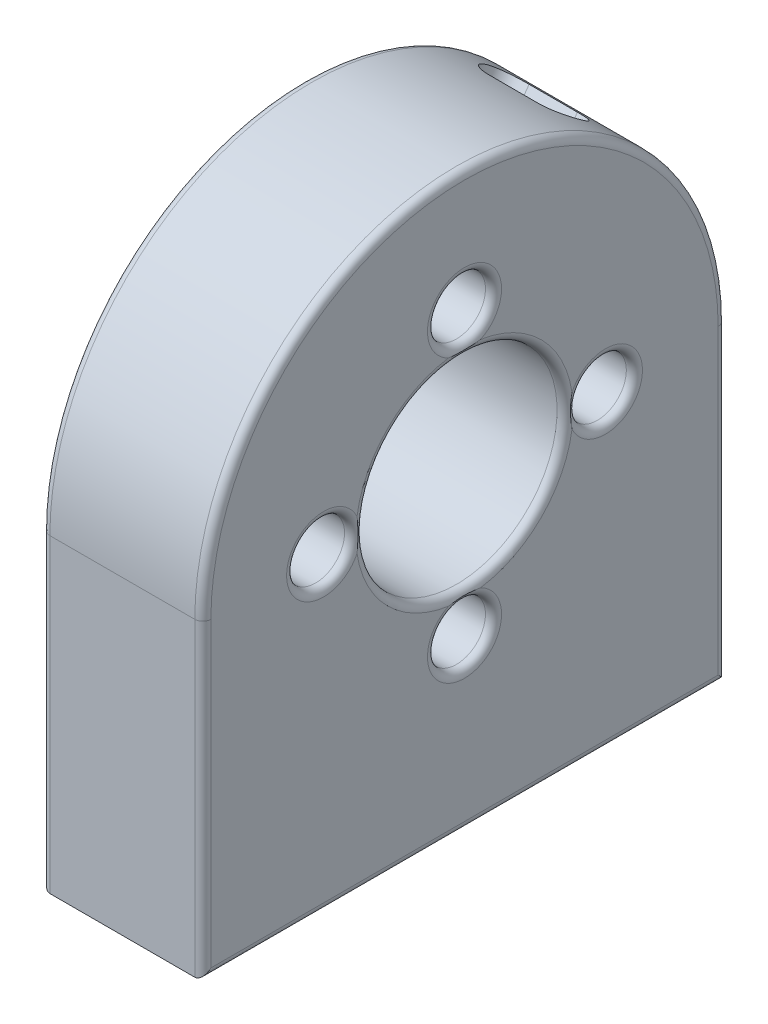
SolidWorks part; units mm, degrees
ref_plane "Ebene vorne" through (0, 0, 0) normal (0, 0, 1) x (1, 0, 0)
ref_plane "Ebene oben" through (0, 0, 0) normal (0, 1, 0) x (1, 0, 0)
ref_plane "Ebene rechts" through (0, 0, 0) normal (1, 0, 0) x (0, 0, -1)
sketch "Skizze1" plane through (0, 0, 0) normal (0, 1, 0) x (1, 0, 0)
  line L1 (-10, -32.5) -> (10, -32.5)
  line L2 (-10, -32.5) -> (-10, 32.5)
  line L3 (-10, 32.5) -> (10, 32.5)
  line L4 (10, -32.5) -> (10, 32.5)
  line L5 (-10, -32.5) -> (10, 32.5) construction
  line L6 (-10, 32.5) -> (10, -32.5) construction
  point P0 (0, 0)
  dimension "D1" = 20
  dimension "D2" = 65
extrude "Aufsatz-Linear austragen1" add sketch "Skizze1" along normal blind 71
sketch "Skizze2" plane through (-10, 0, 0) normal (-1, 0, 0) x (0, 0, 1)
  line L0 (-32.5, 71) -> (32.5, 71) construction
  line L1 (-32.5, 71) -> (-32.5, 0) construction
  line L2 (32.5, 71) -> (32.5, 0) construction
  line L3 (-32.5, 38.5) -> (-32.5, 71)
  line L4 (-32.5, 71) -> (32.5, 71)
  line L5 (32.5, 71) -> (32.5, 38.5)
  circle A0 centre (0, 38.5) radius 32.5
  circle A1 centre (0, 38.5) radius 12.5
  circle A2 centre (0, 38.5) radius 17.5
  circle A3 centre (17.5, 38.5) radius 2.1
  circle A4 centre (0, 21) radius 2.1
  circle A5 centre (-17.5, 38.5) radius 2.1
  circle A6 centre (0, 56) radius 2.1
  point P15 (0, 38.5)
  line M7 (32.5, 0) -> (32.5, 71)
  line M8 (32.5, 71) -> (-32.5, 71)
  line M9 (-32.5, 71) -> (-32.5, 0)
  dimension "D1" = 25
  dimension "D2" = 35
  dimension "D3" = 4
  dimension "D4" = 4.2
extrude "Schnitt-Linear austragen1" cut sketch "Skizze2" against normal through all contours A0 M8 M9 | A0 M7 M8 | A2 A6 | A2 A6 | A2 A5 | A2 A5 | A2 A3 | A2 A3 | A2 A4 | A2 A4 | A1 region at (-10, 63.7405, -25.2405) region at (-10, 63.7405, 25.2405) region at (-10, 38.5, 16.5864) region at (-10, 38.5, 18.3682) region at (-10, 55.0864, 0) region at (-10, 56.8682, 0) region at (-10, 20.1318, 0) region at (-10, 21.9136, 0) region at (-10, 38.5, -16.5864) region at (-10, 38.5, -18.3682)
sketch "Skizze3" plane through (0, 0, 0) normal (0, -1, 0) x (1, 0, 0)
  line L0 (0, 32.5) -> (0, -32.5) construction
  line L1 (-10, 32.5) -> (10, 32.5) construction
  line L2 (10, -32.5) -> (-10, -32.5) construction
  line L4 (0, 0) -> (3.2712, 0) construction
  circle A0 centre (0, 22.5) radius 2.8
  circle A1 centre (0, 10) radius 2.8
  circle A2 centre (0, -10) radius 2.8
  circle A3 centre (0, -22.5) radius 2.8
  dimension "D1" = 5.6
  dimension "D2" = 5.6
  dimension "D3" = 10
  dimension "D4" = 12.5
extrude "Schnitt-Linear austragen2" cut sketch "Skizze3" against normal blind 15 contours A0 | A1 | A2 | A3
sketch "Skizze6" plane through (10, 0, 0) normal (1, 0, 0) x (0, 0, -1)
  circle A1 centre (0, 21) radius 3.6
  circle A7 centre (0, 38.5) radius 12.5
  circle A8 centre (0, 38.5) radius 12.5 construction
  circle A9 centre (-17.5, 38.5) radius 3.6
  circle A10 centre (0, 56) radius 3.6
  circle A11 centre (17.5, 38.5) radius 3.6
  circle A12 centre (0, 21) radius 2.1 construction
  point P22 (0, 38.5)
  circle M3 centre (17.5, 38.5) radius 2.1
  circle M4 centre (0, 56) radius 2.1
  circle M6 centre (-17.5, 38.5) radius 2.1
  circle M7 centre (0, 21) radius 2.1
  dimension "D1" = 4
  dimension "D2" = 7.2
extrude "Schnitt-Linear austragen5" cut sketch "Skizze6" against normal offset from surface (11 mm away) 9 contours A10 M4 | A11 M3 | A9 M6 | M6 | M4 | M3 | M7 | A1 M7 up to face at (-10, 38.5, 12.5)
ref_axis "Achse1" through (10, 38.5, 0) along (-1, 0, 0)
ref_plane "Plane1" through (0, 52.4563, -36.7303) normal (0, 0.8192, -0.5736) x (-1, 0, 0)
sketch "Sketch1" plane through (0, 52.4563, -36.7303) normal (0, 0.8192, -0.5736) x (-1, 0, 0)
  line L0 (-3, 22.0827) -> (3, 22.0827) construction
  line L1 (-3, 25.0827) -> (3, 25.0827)
  line L2 (-3, 19.0827) -> (3, 19.0827)
  line L3 (-10, 22.0827) -> (10, 22.0827) construction
  arc A0 (-3, 25.0827) -> (-3, 19.0827) centre (-3, 22.0827) ccw
  arc A1 (3, 19.0827) -> (3, 25.0827) centre (3, 22.0827) ccw
  point P2 (0, 22.0827)
  dimension "D1" = 6
extrude "Cut-Extrude1" cut sketch "Sketch1" against normal blind 32
fillet "Verrundung1" radius 1 22 edges at (-10, 19.25, 32.5) (-10, 0, 0) (-10, 19.25, -32.5) (-10, 71, 0) (-10, 38.5, -15.4) (-10, 38.5, 19.6) (-10, 56, 2.1) (-10, 21, 2.1) (-10, 38.5, 12.5) (10, 0, 0) (10, 19.25, 32.5) (10, 71, 0) (10, 19.25, -32.5) (10, 38.5, 12.5) (10, 21, -3.6) (10, 38.5, -21.1) (10, 56, -3.6) (10, 38.5, 13.9) (0, 0, -19.7) (0, 0, -7.2) (0, 0, 7.2) (0, 0, 19.7)
